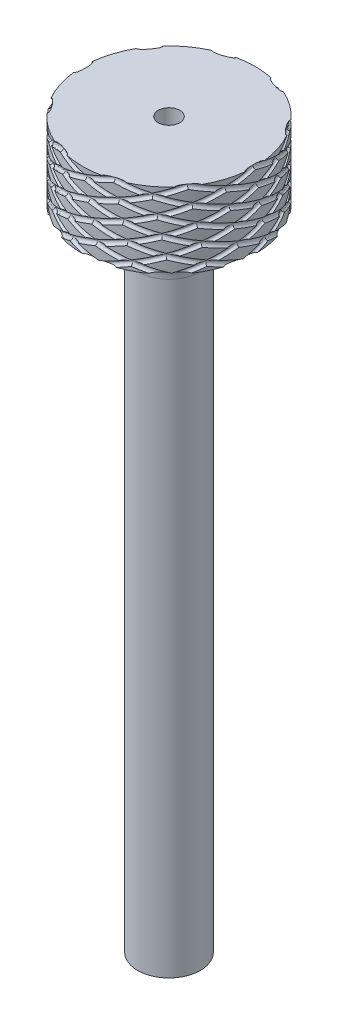
SolidWorks part; units mm, degrees
ref_plane "Front Plane" through (0, 0, 0) normal (0, 0, 1) x (1, 0, 0)
ref_plane "Top Plane" through (0, 0, 0) normal (0, 1, 0) x (1, 0, 0)
ref_plane "Right Plane" through (0, 0, 0) normal (1, 0, 0) x (0, 0, -1)
sketch "Sketch1" plane through (0, 0, 0) normal (0, 1, 0) x (1, 0, 0)
  circle A0 centre (0, 0) radius 2.9
  dimension "D1" = 5.8
extrude "Boss-Extrude1" add sketch "Sketch1" along normal blind 60
sketch "Sketch2" plane through (0, 60, 0) normal (0, 1, 0) x (1, 0, 0)
  circle A0 centre (0, 0) radius 8
extrude "Boss-Extrude2" add sketch "Sketch2" along normal blind 7
sketch "Sketch7" plane through (0, 0, 0) normal (0, -1, 0) x (1, 0, 0)
  circle A0 centre (0, 0) radius 1
  dimension "D1" = 2
extrude "Cut-Extrude1" cut sketch "Sketch7" against normal up to surface (67 mm away) up to face at (0, 67, 8)
fillet "Fillet1" radius 4 1 edges at (0, 60, 2.9)
sketch "Sketch5" plane through (0, 67, 0) normal (0, 1, 0) x (1, 0, 0)
  circle A0 centre (0, 0) radius 8
sketch "Sketch11" plane through (0, 67, 0) normal (0, 1, 0) x (1, 0, 0)
  circle A0 centre (0, 0) radius 8
curve "Helix/Spiral2" pitch 15 height 15 turns 1
sweep "Cut-Sweep2" cut path "Helix/Spiral2" parameters "D3"=0.5
pattern_circular "CirPattern2" count 10 over 360 about axis through (0, 69.8284, 0) along (0, -1, 0) of "Cut-Sweep2"
curve "Helix/Spiral3" pitch 17 height 17 turns 1
sweep "Cut-Sweep4" cut path "Helix/Spiral3" circular profile diameter 0.5 parameters "D3"=0.5
pattern_circular "CirPattern3" count 10 over 360 about axis through (0, 69.8284, 0) along (0, -1, 0) of "Cut-Sweep4"
